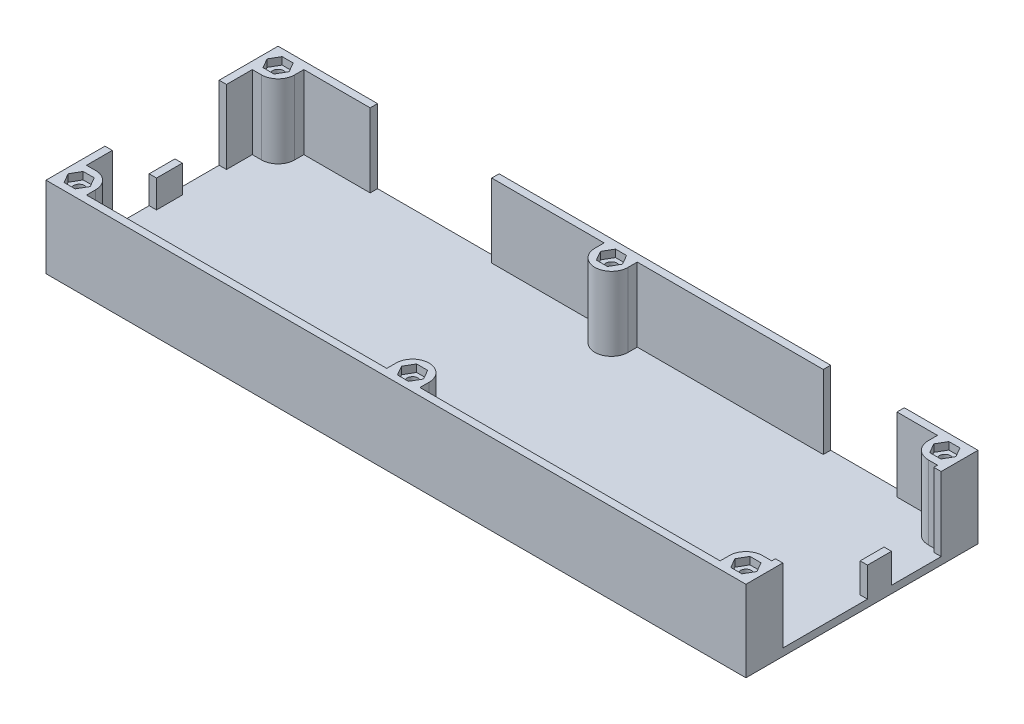
SolidWorks part; units mm, degrees
ref_plane "Front Plane" through (0, 0, 0) normal (0, 0, 1) x (1, 0, 0)
ref_plane "Top Plane" through (0, 0, 0) normal (0, 1, 0) x (1, 0, 0)
ref_plane "Right Plane" through (0, 0, 0) normal (1, 0, 0) x (0, 0, -1)
sketch "Sketch1" plane through (0, 0, 0) normal (0, 1, 0) x (1, 0, 0)
  line L0 (0, 15.9498) -> (0, -13.7203) construction
  line L9 (-95, -31.5) -> (95, -31.5)
  line L10 (-95, -31.5) -> (-95, 31.5)
  line L11 (-95, 31.5) -> (95, 31.5)
  line L12 (95, -31.5) -> (95, 31.5)
  line L13 (-95, -31.5) -> (95, 31.5) construction
  line L14 (-95, 31.5) -> (95, -31.5) construction
  line L15 (-95, 31.5) -> (-86, 31.5)
  line L16 (-95, 31.5) -> (-95, 22.5)
  line L17 (-93, 22.5) -> (-90.5, 22.5)
  line L18 (-86, 29.5) -> (-86, 27)
  line L19 (-23.9463, 0) -> (24.4289, 0) construction
  line L20 (93, 22.5) -> (90.5, 22.5)
  line L21 (86, 29.5) -> (86, 27)
  line L22 (95, 31.5) -> (86, 31.5)
  line L23 (95, 31.5) -> (95, 22.5)
  line L24 (95, -31.5) -> (86, -31.5)
  line L25 (86, -29.5) -> (86, -27)
  line L26 (93, -22.5) -> (90.5, -22.5)
  line L27 (95, -31.5) -> (95, -22.5)
  line L28 (-93, -22.5) -> (-90.5, -22.5)
  line L29 (-86, -29.5) -> (-86, -27)
  line L30 (-95, -31.5) -> (-86, -31.5)
  line L31 (-95, -31.5) -> (-95, -22.5)
  line L35 (-4.5, 31.5) -> (4.5, 31.5)
  line L37 (-4.5, 22.5) -> (4.5, 31.5) construction
  line L38 (-4.5, 31.5) -> (4.5, 22.5) construction
  line L42 (-95, 31.5) -> (-86, 22.5) construction
  line L43 (-95, 22.5) -> (-86, 31.5) construction
  line L44 (92, 29.5981) -> (93.5, 27)
  line L45 (-93.5, 27) -> (-92, 24.4019)
  line L46 (-92, 24.4019) -> (-89, 24.4019)
  line L47 (-89, 24.4019) -> (-87.5, 27)
  line L48 (-87.5, 27) -> (-89, 29.5981)
  line L49 (-89, 29.5981) -> (-92, 29.5981)
  line L50 (-92, 29.5981) -> (-93.5, 27)
  line L51 (89, 29.5981) -> (92, 29.5981)
  line L52 (87.5, 27) -> (89, 29.5981)
  line L53 (89, 24.4019) -> (87.5, 27)
  line L54 (92, 24.4019) -> (89, 24.4019)
  line L55 (93.5, 27) -> (92, 24.4019)
  line L56 (89, -29.5981) -> (92, -29.5981)
  line L57 (87.5, -27) -> (89, -29.5981)
  line L58 (89, -24.4019) -> (87.5, -27)
  line L59 (92, -24.4019) -> (89, -24.4019)
  line L60 (93.5, -27) -> (92, -24.4019)
  line L61 (92, -29.5981) -> (93.5, -27)
  line L62 (-92, -29.5981) -> (-93.5, -27)
  line L63 (-89, -29.5981) -> (-92, -29.5981)
  line L64 (-87.5, -27) -> (-89, -29.5981)
  line L65 (-89, -24.4019) -> (-87.5, -27)
  line L66 (-92, -24.4019) -> (-89, -24.4019)
  line L67 (-93.5, -27) -> (-92, -24.4019)
  line L80 (-4.5, 31.5) -> (-4.5, 22.5) construction
  line L81 (4.5, 31.5) -> (4.5, 22.5) construction
  line L82 (4.5, 22.5) -> (-4.5, 22.5) construction
  line L83 (-4.5, 29.5) -> (-4.5, 27)
  line L84 (4.5, 29.5) -> (4.5, 27)
  line L85 (4.5, -29.5) -> (4.5, -27)
  line L92 (-4.5, -29.5) -> (-4.5, -27)
  line L93 (1.5, -24.4019) -> (3, -27)
  line L94 (3, 27) -> (1.5, 29.5981)
  line L95 (1.5, 29.5981) -> (-1.5, 29.5981)
  line L96 (-1.5, 29.5981) -> (-3, 27)
  line L97 (-3, 27) -> (-1.5, 24.4019)
  line L98 (-1.5, 24.4019) -> (1.5, 24.4019)
  line L99 (1.5, 24.4019) -> (3, 27)
  line L106 (-1.5, -24.4019) -> (1.5, -24.4019)
  line L107 (-3, -27) -> (-1.5, -24.4019)
  line L108 (-1.5, -29.5981) -> (-3, -27)
  line L109 (1.5, -29.5981) -> (-1.5, -29.5981)
  line L110 (3, -27) -> (1.5, -29.5981)
  line L111 (-86, 29.5) -> (-4.5, 29.5)
  line L112 (-93, 22.5) -> (-93, -22.5)
  line L113 (-86, -29.5) -> (-4.5, -29.5)
  line L114 (4.5, -29.5) -> (86, -29.5)
  line L115 (93, -22.5) -> (93, 22.5)
  line L116 (86, 29.5) -> (4.5, 29.5)
  circle A0 centre (-90.5, 27) radius 1.5
  circle A1 centre (-90.5, 27) radius 2.5981 construction
  circle A2 centre (90.5, 27) radius 1.5
  circle A3 centre (90.5, -27) radius 1.5
  circle A4 centre (-90.5, -27) radius 1.5
  circle A5 centre (0, 27) radius 1.5
  circle A6 centre (0, 27) radius 2.5981 construction
  arc A8 (-90.5, 22.5) -> (-86, 27) centre (-90.5, 27) ccw
  arc A9 (-4.5, 27) -> (4.5, 27) centre (0, 27) ccw
  circle A10 centre (0, -27) radius 1.5
  arc A11 (-4.5, -27) -> (4.5, -27) centre (0, -27) cw
  arc A12 (-86, -27) -> (-90.5, -22.5) centre (-90.5, -27) ccw
  arc A13 (86, -27) -> (90.5, -22.5) centre (90.5, -27) cw
  arc A14 (86, 27) -> (90.5, 22.5) centre (90.5, 27) ccw
  point P0 (0, 0)
  point P22 (0, 27)
  point P27 (0, 31.5)
  point P28 (0, 31.5)
  point P91 (-86, -22.5)
  point P94 (86, -22.5)
  point P97 (86, 22.5)
  dimension "D7" = 3
  dimension "D10" = 3
  dimension "D13" = 4.5
  dimension "D14" = 4.5
  dimension "D15" = 4.5
  dimension "D16" = 4.5
  dimension "D17" = 2
  dimension "D11" = 6
  dimension "D1" = 190
  dimension "D2" = 63
  dimension "D3" = 9
  dimension "D4" = 9
  dimension "D5" = 9
  dimension "D6" = 9
  dimension "D8" = 6
  dimension "D9" = 1.5
  dimension "D12" = 1.5
  dimension "D18" = 2
  dimension "D19" = 2
  dimension "D20" = 2
  dimension "D21" = 2
  dimension "D22" = 2
  dimension "D23" = 4.5
  dimension "D24" = 4.5
  dimension "D25" = 2
  dimension "D26" = 2
  dimension "D27" = 2
  dimension "D28" = 2
  dimension "D29" = 4.5
  dimension "D30" = 4.5
  dimension "D31" = 2
  dimension "D32" = 2
extrude "Boss-Extrude1" add sketch "Sketch1" along normal blind 2 contours A14 L21 L116 L84 A9 L83 L111 L18 A8 L17 L112 L28 A12 L29 L113 L92 A11 L85 L114 L25 A13 L26 L115 L20 region at (0, 0, 0)
extrude "Boss-Extrude2" add sketch "Sketch1<4>" along normal blind 19 separate body contours A2 | A3 | A10 | A5 | A0 | A4 region at (-90.5, 0, -27) region at (90.5, 0, -27) region at (90.5, 0, 27) region at (0, 0, -27) region at (0, 0, 27)
sketch "Sketch1<4>" plane through (0, 0, 0) normal (0, 1, 0) x (1, 0, 0) same geometry as "Sketch1"
extrude "Boss-Extrude3" add sketch "Sketch1<5>" along normal blind 20 contours L55 L44 L51 L52 L53 L54 A2 | L56 L61 L60 L59 L58 L57 A3 | L110 L93 L106 L107 L108 L109 A10 | L98 L99 L94 L95 L96 L97 A5 | L67 L62 L63 L64 L65 L66 A4 | L49 L50 L45 L46 L47 L48 A0 region at (92.6813, 0, -28.2594) region at (-92.6813, 0, -28.2594) region at (88.3187, 0, 28.2594) region at (-92.6813, 0, 28.2594) region at (2.1813, 0, 25.7406) region at (2.1813, 0, -25.7406)
sketch "Sketch1<5>" plane through (0, 0, 0) normal (0, 1, 0) x (1, 0, 0) same geometry as "Sketch1"
extrude "Boss-Extrude4" add sketch "Sketch1<6>" along normal blind 22 contours L9 L12 L11 L10 L99 L98 L97 L96 L95 L94 L61 L56 L57 L58 L59 L60 L50 L49 L48 L47 L46 L45 L44 L55 L54 L53 L52 L51 L62 L67 L66 L65 L64 L63 L93 region at (-94.7998, 0, 27)
sketch "Sketch1<6>" plane through (0, 0, 0) normal (0, 1, 0) x (1, 0, 0) same geometry as "Sketch1"
sketch "Sketch2" plane through (95, 0, 0) normal (1, 0, 0) x (0, 0, -1)
  line L0 (-22.5, 2) -> (22.5, 2) construction
  line L1 (-22.5, 12.0332) -> (-22.5, 2) construction
  line L2 (-31.5, 22) -> (-31.5, 0) construction
  line L3 (-31.5, 0) -> (31.5, 0) construction
  line L4 (31.5, 22) -> (31.5, 0) construction
  line L5 (-21.5, 2) -> (1.5, 2)
  line L6 (-21.5, 2) -> (-21.5, 10)
  line L7 (-21.5, 10) -> (1.5, 10)
  line L8 (1.5, 2) -> (1.5, 10)
  line L10 (8, 2) -> (21.5, 2)
  line L11 (8, 2) -> (8, 15.3)
  line L12 (8, 15.3) -> (21.5, 15.3)
  line L13 (21.5, 2) -> (21.5, 15.3)
  dimension "D1" = 9
  dimension "D2" = 2
  dimension "D3" = 9
  dimension "D4" = 23
  dimension "D5" = 8
  dimension "D6" = 10
  dimension "D7" = 13.3
  dimension "D8" = 13.5
  dimension "D9" = 10
extrude "Cut-Extrude1" cut sketch "Sketch2" against normal blind 3
sketch "Sketch3" plane through (0, 0, -31.5) normal (0, 0, -1) x (-1, 0, 0)
  line L0 (-95, 22) -> (-95, 0) construction
  line L1 (-75, 2) -> (-55, 2)
  line L2 (-75, 2) -> (-75, 14)
  line L3 (-75, 14) -> (-55, 14)
  line L4 (-55, 2) -> (-55, 14)
  line L5 (95, 0) -> (-95, 0) construction
  line L6 (95, 22) -> (95, 0) construction
  line L7 (35, 2) -> (68, 2)
  line L8 (35, 2) -> (35, 14)
  line L9 (35, 14) -> (68, 14)
  line L10 (68, 2) -> (68, 14)
  dimension "D1" = 20
  dimension "D2" = 20
  dimension "D3" = 2
  dimension "D4" = 12
  dimension "D5" = 60
  dimension "D6" = 33
  dimension "D7" = 2
  dimension "D8" = 12
extrude "Cut-Extrude2" cut sketch "Sketch3" against normal blind 3
sketch "Sketch4" plane through (-95, 0, 0) normal (-1, 0, 0) x (0, 0, 1)
  line L0 (0, 0) -> (0, 22) construction
  line L1 (31.5, 22) -> (-31.5, 22) construction
  line L2 (31.5, 0) -> (-31.5, 0) construction
  line L3 (-15.5, 2) -> (-3.5, 2)
  line L4 (-15.5, 2) -> (-15.5, 9.5)
  line L5 (-15.5, 9.5) -> (-3.5, 9.5)
  line L6 (-3.5, 2) -> (-3.5, 9.5)
  line L7 (-31.5, 22) -> (-31.5, 0) construction
  line L8 (15.5, 9.5) -> (3.5, 9.5)
  line L9 (3.5, 2) -> (3.5, 9.5)
  line L10 (15.5, 2) -> (3.5, 2)
  line L11 (15.5, 2) -> (15.5, 9.5)
  dimension "D1" = 2
  dimension "D2" = 12
  dimension "D3" = 7.5
  dimension "D4" = 16
extrude "Cut-Extrude3" cut sketch "Sketch4" against normal blind 3
sketch "Sketch5" plane through (95, 0, 0) normal (1, 0, 0) x (0, 0, -1)
  line L0 (-21.5, 10) -> (-21.5, 22)
  line L1 (-31.5, 22) -> (31.5, 22) construction
  line L2 (-21.5, 10) -> (8, 10)
  line L3 (8, 15.3) -> (8, 2) construction
  line L4 (8, 10) -> (8, 15.3)
  line L5 (8, 15.3) -> (21.5, 15.3)
  line L6 (21.5, 15.3) -> (21.5, 22)
sketch "Sketch6" plane through (0, 0, -31.5) normal (0, 0, -1) x (-1, 0, 0)
  line L0 (-55, 2) -> (-55, 14) construction
  line L1 (95, 22) -> (-95, 22) construction
  line L2 (-75, 14) -> (-55, 14)
  line L3 (68, 2) -> (68, 14) construction
  line L4 (35, 14) -> (68, 14)
  line L5 (-75, 14) -> (-75, 22)
  line L9 (35, 14) -> (35, 22)
  line L10 (-75, 22) -> (-55, 22)
  line L11 (-55, 14) -> (-55, 22)
  line L12 (35, 22) -> (68, 22)
  line L13 (68, 14) -> (68, 22)
sketch "Sketch7" plane through (-95, 0, 0) normal (-1, 0, 0) x (0, 0, 1)
  line L0 (-15.5, 9.5) -> (-15.5, 22)
  line L1 (31.5, 22) -> (-31.5, 22) construction
  line L2 (-15.5, 9.5) -> (15.5, 9.5)
  line L3 (15.5, 9.5) -> (15.5, 22)
  line L4 (15.5, 9.5) -> (3.5, 9.5) construction
  line L5 (15.5, 2) -> (15.5, 9.5) construction
extrude "Cut-Extrude4" cut sketch "Sketch5" against normal blind 2 and the other way through all
extrude "Cut-Extrude5" cut sketch "Sketch6" against normal blind 2
extrude "Cut-Extrude6" cut sketch "Sketch7" against normal blind 2 and the other way through all
